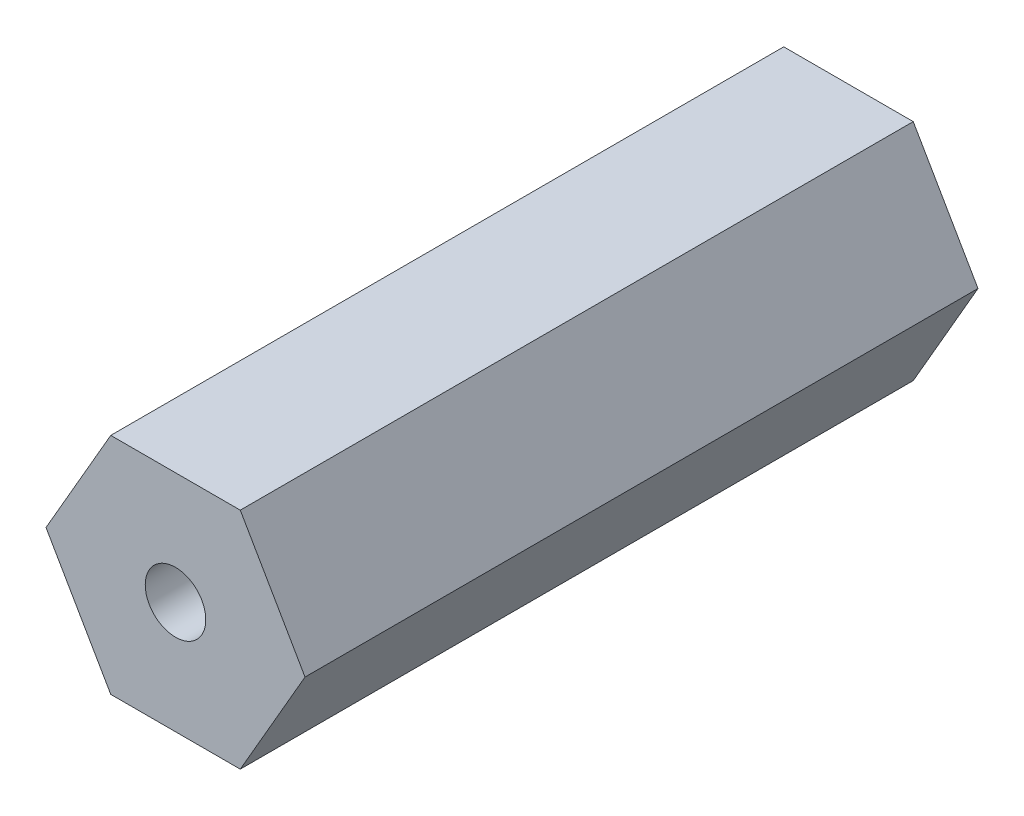
SolidWorks part; units mm, degrees
material "7075-T6 (SN)"
ref_plane "Front Plane" through (0, 0, 0) normal (0, 0, 1) x (1, 0, 0)
ref_plane "Top Plane" through (0, 0, 0) normal (0, 1, 0) x (1, 0, 0)
ref_plane "Right Plane" through (0, 0, 0) normal (1, 0, 0) x (0, 0, -1)
other "Configuration Table"
sketch "Sketch1" plane through (0, 0, 0) normal (0, 0, 1) x (1, 0, 0)
  line L1 (7.3323, 0) -> (3.6662, 6.35)
  line L2 (3.6662, 6.35) -> (-3.6662, 6.35)
  line L3 (-3.6662, 6.35) -> (-7.3323, 0)
  line L4 (-7.3323, 0) -> (-3.6662, -6.35)
  line L5 (-3.6662, -6.35) -> (3.6662, -6.35)
  line L6 (3.6662, -6.35) -> (7.3323, 0)
  circle A0 centre (0, 0) radius 6.35 construction
  circle A1 centre (0, 0) radius 1.7145
  dimension "D2" = 3.429
  dimension "D1" = 12.7
extrude "Boss-Extrude1" add sketch "Sketch1" along normal mid plane 38.1
fillet "Fillet1" [suppressed] radius 0.635
equation "\"length\"= 1.5"
equation "\"D1@Boss-Extrude1\"=\"length\""
